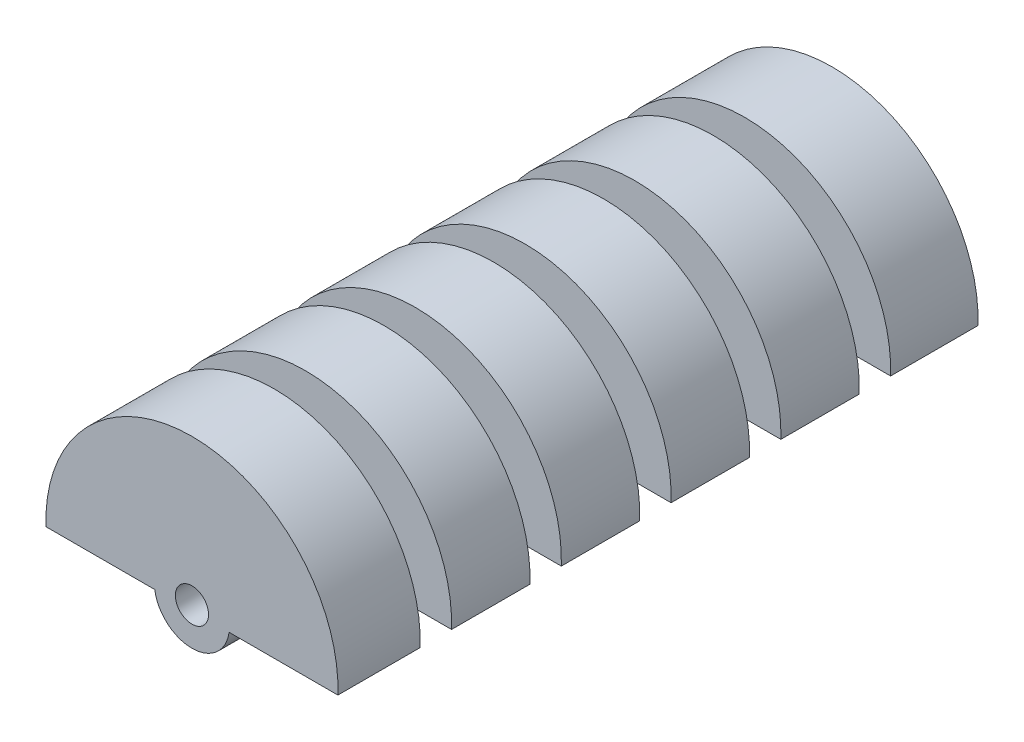
SolidWorks part; units mm, degrees
material "RUBBER 65A Test Modulus"
ref_plane "Front Plane" through (0, 0, 0) normal (0, 0, 1) x (1, 0, 0)
ref_plane "Top Plane" through (0, 0, 0) normal (0, 1, 0) x (1, 0, 0)
ref_plane "Right Plane" through (0, 0, 0) normal (1, 0, 0) x (0, 0, -1)
sketch "Sketch3" plane through (0, 0, 0) normal (0, 0, 1) x (1, 0, 0)
  circle A0 centre (0, 0) radius 27.94
  dimension "D1" = 55.88
extrude "Boss-Extrude2" add sketch "Sketch3" along normal blind 122.46
ref_axis "Axis2" through (0, 0, 121.5887) along (0, 0, -1)
sketch "Sketch5" plane through (0, 0, 122.46) normal (0, 0, 1) x (1, 0, 0)
  circle A0 centre (0, 0) radius 3.175
  dimension "D1" = 6.35
extrude "Cut-Extrude1" cut sketch "Sketch5" against normal through all contours A0
sketch "Sketch4" plane through (0, 0, 0) normal (0, 1, 0) x (1, 0, 0)
  line L0 (0, -122.46) -> (0, 0) construction
  line L1 (-27.94, -122.46) -> (27.94, -122.46) construction
  line L3 (-27.94, -106.72) -> (-13.94, -106.72)
  line L4 (-27.94, -106.72) -> (-27.94, -100.72)
  line L5 (-27.94, -100.72) -> (-13.94, -100.72)
  line L6 (-13.94, -106.72) -> (-13.94, -100.72)
  line L63 (-27.94, -85.72) -> (-27.94, -79.72)
  line L64 (-27.94, -85.72) -> (-13.94, -85.72)
  line L65 (-13.94, -85.72) -> (-13.94, -79.72)
  line L66 (-27.94, -79.72) -> (-13.94, -79.72)
  line L67 (-27.94, -64.72) -> (-27.94, -58.72)
  line L68 (-27.94, -64.72) -> (-13.94, -64.72)
  line L69 (-13.94, -64.72) -> (-13.94, -58.72)
  line L70 (-27.94, -58.72) -> (-13.94, -58.72)
  line L71 (-27.94, -43.72) -> (-27.94, -37.72)
  line L72 (-27.94, -43.72) -> (-13.94, -43.72)
  line L73 (-13.94, -43.72) -> (-13.94, -37.72)
  line L74 (-27.94, -37.72) -> (-13.94, -37.72)
  line L75 (-27.94, -22.72) -> (-27.94, -16.72)
  line L76 (-27.94, -22.72) -> (-13.94, -22.72)
  line L77 (-13.94, -22.72) -> (-13.94, -16.72)
  line L78 (-27.94, -16.72) -> (-13.94, -16.72)
  line L91 (-27.94, -106.72) -> (-27.94, -85.72) construction
  line L92 (-27.94, -1.72) -> (-27.94, 4.28) [skipped]
  line L93 (-27.94, -1.72) -> (-13.94, -1.72) [skipped]
  line L94 (-13.94, -1.72) -> (-13.94, 4.28) [skipped]
  line L95 (-27.94, 4.28) -> (-13.94, 4.28) [skipped]
  line L96 (-27.94, 19.28) -> (-27.94, 25.28) [skipped]
  line L97 (-27.94, 19.28) -> (-13.94, 19.28) [skipped]
  line L98 (-13.94, 19.28) -> (-13.94, 25.28) [skipped]
  line L99 (-27.94, 25.28) -> (-13.94, 25.28) [skipped]
  line L100 (-27.94, 40.28) -> (-27.94, 46.28) [skipped]
  line L101 (-27.94, 40.28) -> (-13.94, 40.28) [skipped]
  line L102 (-13.94, 40.28) -> (-13.94, 46.28) [skipped]
  line L103 (-27.94, 46.28) -> (-13.94, 46.28) [skipped]
  dimension "D1" = 15.74
  dimension "D2" = 6
  dimension "D3" = 27.94
  dimension "D4" = 14
  dimension "D6" = 21
  dimension "D5" = 8
revolve "Cut-Revolve1" cut sketch "Sketch4" angle 360 about L0
shell "Shell1" thickness 3
sketch "Sketch10" plane through (0, 0, 0) normal (0, 0, -1) x (-1, 0, 0)
  line L0 (0, 27.94) -> (0, -27.94) construction
  line L1 (-27.94, 0) -> (27.94, 0) construction
  line L2 (-1, 27.9221) -> (-1, 3.0134)
  line L3 (1, 3.0134) -> (1, 27.9221)
  line L4 (3.0134, 1) -> (27.9221, 1)
  line L5 (3.0134, -1) -> (27.9221, -1)
  line L6 (-1, -3.0134) -> (-1, -27.9221)
  line L7 (1, -3.0134) -> (1, -27.9221)
  line L8 (-27.9221, -1) -> (-3.0134, -1)
  line L9 (-27.9221, 1) -> (-3.0134, 1)
  circle A0 centre (0, 0) radius 27.94 construction
  circle A1 centre (0, 0) radius 3.175 construction
  arc A2 (-1, -27.9221) -> (1, -27.9221) centre (0, 0) ccw
  arc A3 (27.9221, -1) -> (27.9221, 1) centre (0, 0) ccw
  arc A4 (1, 27.9221) -> (-1, 27.9221) centre (0, 0) ccw
  arc A5 (-27.9221, 1) -> (-27.9221, -1) centre (0, 0) ccw
  arc A6 (-1, -3.0134) -> (1, -3.0134) centre (0, 0) ccw
  arc A7 (-3.0134, 1) -> (-3.0134, -1) centre (0, 0) ccw
  arc A8 (1, 3.0134) -> (-1, 3.0134) centre (0, 0) ccw
  arc A9 (3.0134, -1) -> (3.0134, 1) centre (0, 0) ccw
  dimension "D1" = 1
  dimension "D2" = 1
  dimension "D3" = 1
  dimension "D4" = 1
  dimension "D5" = 1
extrude "Boss-Extrude3" add sketch "Sketch10" against normal up to surface (122.46 mm away) up to face at (3.175, 0, 122.46)
ref_plane "Plane1" through (0, 0, 0) normal (-0.7071, -0.7071, 0) x (0, 0, -1)
ref_plane "Plane2" through (0, 0, 0) normal (-0.7071, 0.7071, 0) x (0, 0, -1)
ref_plane "Plane3" through (0, 0, 0) normal (0, 1, 0) x (1, 0, 0)
sketch "Sketch13" plane through (0, 0, 0) normal (0, 1, 0) x (1, 0, 0)
  line L0 (-30.3872, -37.72) -> (-13.9041, -37.72)
  line L1 (-30.3872, -16.72) -> (-13.9041, -16.72)
  line L2 (-30.3872, -16.72) -> (-30.3872, -22.72)
  line L3 (-30.3872, -22.72) -> (-13.9041, -22.72)
  line L4 (-13.9041, -16.72) -> (-13.9041, -22.72)
  line L5 (-30.3872, -37.72) -> (-30.3872, -43.72)
  line L6 (-30.3872, -43.72) -> (-13.9041, -43.72)
  line L7 (-13.9041, -37.72) -> (-13.9041, -43.72)
  line L8 (-30.3872, -58.72) -> (-13.9041, -58.72)
  line L9 (-30.3872, -58.72) -> (-30.3872, -64.72)
  line L10 (-30.3872, -64.72) -> (-13.9041, -64.72)
  line L11 (-13.9041, -58.72) -> (-13.9041, -64.72)
  line L12 (-30.3872, -79.72) -> (-13.9041, -79.72)
  line L13 (-30.3872, -79.72) -> (-30.3872, -85.72)
  line L14 (-30.3872, -85.72) -> (-13.9041, -85.72)
  line L15 (-13.9041, -79.72) -> (-13.9041, -85.72)
  line L16 (-30.3872, -100.72) -> (-13.9041, -100.72)
  line L17 (-30.3872, -100.72) -> (-30.3872, -106.72)
  line L18 (-30.3872, -106.72) -> (-13.9041, -106.72)
  line L19 (-13.9041, -100.72) -> (-13.9041, -106.72)
  dimension "D2" = 6
  dimension "D1" = 5
revolve "Cut-Revolve2" cut sketch "Sketch13" angle 360 about axis through (0, 0, 121.5887) along (0, 0, -1)
sketch "Sketch15" plane through (0, 0, 0) normal (0, 0, -1) x (-1, 0, 0)
  line L0 (0, 0) -> (0, 28.5004) construction
  line L1 (0, 0) -> (-22.0052, 22.0052) construction
sketch "Sketch16" plane through (0, 0, 0) normal (0, 0, -1) x (-1, 0, 0)
  line L0 (-3.175, 0) -> (-6.9755, 0) construction
  line L1 (-27.94, 0) -> (27.94, 0) construction
  line L2 (3.175, 0) -> (7.175, 0) construction
  line L3 (-6.9755, 0) -> (-6.9755, -0.971) construction
  line L4 (-6.9755, -0.971) -> (-6.6911, -0.971) construction
  line L5 (7.175, 0) -> (7.175, -1) construction
  line L8 (-3.175, 0) -> (-6.175, 0) construction
  line L9 (3.175, 0) -> (6.175, 0) construction
  line L10 (-27.9231, -0.971) -> (-6.0982, -0.971)
  line L11 (27.9221, -1) -> (6.0935, -1)
  arc A0 (-27.9231, -0.971) -> (27.9221, -1) centre (0, 0) ccw
  circle A1 centre (0, 0) radius 27.94 construction
  circle A2 centre (0, 0) radius 3.175 construction
  arc A5 (-6.0982, -0.971) -> (6.0935, -1) centre (0, 0) ccw
extrude "Cut-Extrude3" cut sketch "Sketch16" against normal blind 123
sketch "Sketch17" plane through (0, 0, 0) normal (0, 0, -1) x (-1, 0, 0)
  line L0 (-3.175, 0) -> (-7.175, 0) construction
  line L1 (3.175, 0) -> (7.175, 0) construction
  line L2 (-3.175, 0) -> (-7.175, 0)
  line L3 (3.175, 0) -> (7.175, 0)
  circle A0 centre (0, 0) radius 3.175 construction
  arc A1 (-7.175, 0) -> (7.175, 0) centre (0, 0) ccw
  arc A2 (-3.175, 0) -> (3.175, 0) centre (0, 0) ccw
  line M2 (-27.9231, -0.971) -> (-6.0982, -0.971)
  arc M3 (-6.0982, -0.971) -> (6.0935, -1) centre (0, 0) ccw
  line M4 (6.0935, -1) -> (27.9221, -1)
extrude "Boss-Extrude4" add sketch "Sketch17" against normal blind 122.46 contours A1 M2 M4 M3 region at (6.6036, -1.1261, 0)
equation "\"inwall\"= .75"
equation "\"outwall\"=2"
